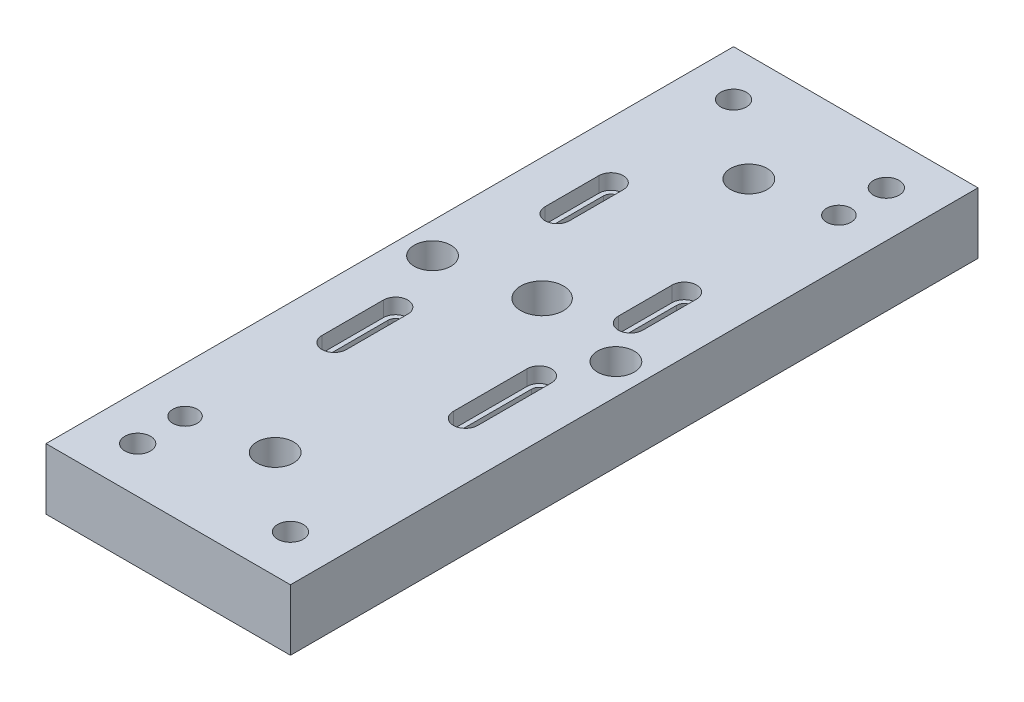
SolidWorks part; units mm, degrees
material "Plain Carbon Steel"
ref_plane "Front Plane" through (0, 0, 0) normal (0, 0, 1) x (1, 0, 0)
ref_plane "Top Plane" through (0, 0, 0) normal (0, 1, 0) x (1, 0, 0)
ref_plane "Right Plane" through (0, 0, 0) normal (1, 0, 0) x (0, 0, -1)
sketch "Sketch1" plane through (0, 0, 0) normal (0, 1, 0) x (1, 0, 0)
  line L1 (-40, -112.5) -> (40, -112.5)
  line L2 (-40, -112.5) -> (-40, 112.5)
  line L3 (-40, 112.5) -> (40, 112.5)
  line L4 (40, -112.5) -> (40, 112.5)
  line L5 (-40, -112.5) -> (40, 112.5) construction
  line L6 (-40, 112.5) -> (40, -112.5) construction
  point P0 (0, 0)
  dimension "D1" = 225
  dimension "D2" = 80
extrude "Boss-Extrude1" add sketch "Sketch1" against normal blind 20
sketch "Sketch2" plane through (0, 0, 0) normal (0, 1, 0) x (1, 0, 0)
  line L4 (24, 17.31) -> (24, 34.91)
  line L5 (19, 34.91) -> (19, 17.31)
  line L6 (24, 17.31) -> (24, 34.91)
  line L7 (19, 34.91) -> (19, 17.31)
  line L10 (24, -36.69) -> (24, -12.59)
  line L11 (19, -12.59) -> (19, -36.69)
  line L12 (24, -36.69) -> (24, -12.59)
  line L13 (19, -12.59) -> (19, -36.69)
  line L16 (-24, -16.59) -> (-24, -36.69)
  line L17 (-19, -36.69) -> (-19, -16.59)
  line L18 (-24, -16.59) -> (-24, -36.69)
  line L19 (-19, -36.69) -> (-19, -16.59)
  line L22 (-24, 53.91) -> (-24, 36.31)
  line L23 (-19, 36.31) -> (-19, 53.91)
  line L24 (-24, 53.91) -> (-24, 36.31)
  line L25 (-19, 36.31) -> (-19, 53.91)
  arc A4 (24, 34.91) -> (19, 34.91) centre (21.5, 34.91) ccw
  arc A5 (19, 17.31) -> (24, 17.31) centre (21.5, 17.31) ccw
  arc A6 (24, 34.91) -> (19, 34.91) centre (21.5, 34.91) ccw
  arc A7 (19, 17.31) -> (24, 17.31) centre (21.5, 17.31) ccw
  arc A10 (24, -12.59) -> (19, -12.59) centre (21.5, -12.59) ccw
  arc A11 (19, -36.69) -> (24, -36.69) centre (21.5, -36.69) ccw
  arc A12 (24, -12.59) -> (19, -12.59) centre (21.5, -12.59) ccw
  arc A13 (19, -36.69) -> (24, -36.69) centre (21.5, -36.69) ccw
  arc A16 (-24, -36.69) -> (-19, -36.69) centre (-21.5, -36.69) ccw
  arc A17 (-19, -16.59) -> (-24, -16.59) centre (-21.5, -16.59) ccw
  arc A18 (-24, -36.69) -> (-19, -36.69) centre (-21.5, -36.69) ccw
  arc A19 (-19, -16.59) -> (-24, -16.59) centre (-21.5, -16.59) ccw
  arc A22 (-24, 36.31) -> (-19, 36.31) centre (-21.5, 36.31) ccw
  arc A23 (-19, 53.91) -> (-24, 53.91) centre (-21.5, 53.91) ccw
  arc A24 (-24, 36.31) -> (-19, 36.31) centre (-21.5, 36.31) ccw
  arc A25 (-19, 53.91) -> (-24, 53.91) centre (-21.5, 53.91) ccw
  dimension "D2" = 0.05
  dimension "D1" = 0.05
  dimension "D3" = 0.05
  dimension "D4" = 0.05
extrude "Cut-Extrude1" cut sketch "Sketch2" against normal up to next
sketch "Sketch3" plane through (0, 0, 0) normal (0, 1, 0) x (1, 0, 0)
  line L4 (-17.5, 36.31) -> (-17.5, 53.91)
  line L5 (-25.5, 53.91) -> (-25.5, 36.31)
  line L6 (-17.5, 36.31) -> (-17.5, 53.91)
  line L7 (-25.5, 53.91) -> (-25.5, 36.31)
  line L10 (25.5, 17.31) -> (25.5, 34.91)
  line L11 (17.5, 34.91) -> (17.5, 17.31)
  line L12 (25.5, 17.31) -> (25.5, 34.91)
  line L13 (17.5, 34.91) -> (17.5, 17.31)
  line L16 (25.5, -36.69) -> (25.5, -12.59)
  line L17 (17.5, -12.59) -> (17.5, -36.69)
  line L18 (25.5, -36.69) -> (25.5, -12.59)
  line L19 (17.5, -12.59) -> (17.5, -36.69)
  line L22 (-25.5, -16.59) -> (-25.5, -36.69)
  line L23 (-17.5, -36.69) -> (-17.5, -16.59)
  line L24 (-25.5, -16.59) -> (-25.5, -36.69)
  line L25 (-17.5, -36.69) -> (-17.5, -16.59)
  arc A4 (-17.5, 53.91) -> (-25.5, 53.91) centre (-21.5, 53.91) ccw
  arc A5 (-25.5, 36.31) -> (-17.5, 36.31) centre (-21.5, 36.31) ccw
  arc A6 (-17.5, 53.91) -> (-25.5, 53.91) centre (-21.5, 53.91) ccw
  arc A7 (-25.5, 36.31) -> (-17.5, 36.31) centre (-21.5, 36.31) ccw
  arc A10 (25.5, 34.91) -> (17.5, 34.91) centre (21.5, 34.91) ccw
  arc A11 (17.5, 17.31) -> (25.5, 17.31) centre (21.5, 17.31) ccw
  arc A12 (25.5, 34.91) -> (17.5, 34.91) centre (21.5, 34.91) ccw
  arc A13 (17.5, 17.31) -> (25.5, 17.31) centre (21.5, 17.31) ccw
  arc A16 (25.5, -12.59) -> (17.5, -12.59) centre (21.5, -12.59) ccw
  arc A17 (17.5, -36.69) -> (25.5, -36.69) centre (21.5, -36.69) ccw
  arc A18 (25.5, -12.59) -> (17.5, -12.59) centre (21.5, -12.59) ccw
  arc A19 (17.5, -36.69) -> (25.5, -36.69) centre (21.5, -36.69) ccw
  arc A22 (-25.5, -36.69) -> (-17.5, -36.69) centre (-21.5, -36.69) ccw
  arc A23 (-17.5, -16.59) -> (-25.5, -16.59) centre (-21.5, -16.59) ccw
  arc A24 (-25.5, -36.69) -> (-17.5, -36.69) centre (-21.5, -36.69) ccw
  arc A25 (-17.5, -16.59) -> (-25.5, -16.59) centre (-21.5, -16.59) ccw
  dimension "D1" = 1.5
  dimension "D2" = 1.5
  dimension "D3" = 1.5
  dimension "D4" = 1.5
extrude "Cut-Extrude2" cut sketch "Sketch3" against normal blind 5
hole_wizard "CBORE for M8 Hex Socket Head Cap Screw1" positions "Sketch7" profile "Sketch6" counterbore size "M8" standard "ISO" end condition through all
sketch "Sketch7" plane through (0, -20, 0) normal (0, -1, 0) x (-1, 0, 0)
  line L0 (-40, -112.5) -> (-40, 112.5) construction
  line L1 (-40, 112.5) -> (40, 112.5) construction
  line L2 (40, 112.5) -> (40, -112.5) construction
  line L3 (40, -112.5) -> (-40, -112.5) construction
  point P0 (-25, 97.5)
  point P2 (25, 97.5)
  point P4 (25, -97.5)
  point P6 (-25, -97.5)
  dimension "D1" = 15
  dimension "D2" = 15
  dimension "D3" = 15
  dimension "D4" = 15
sketch "Sketch6" plane through (25, -20, -97.5) normal (1, 0, 0) x (0, 0, -1)
  line L0 (0, 0) -> (0, 20)
  line L1 (0, 20) -> (4.2, 20)
  line L3 (4.2, 20) -> (4.2, 8.6)
  line L4 (7.5, 8.6) -> (4.2, 8.6)
  line L5 (7.5, 8.6) -> (7.5, 0.025)
  line L6 (7.5, 0.025) -> (7.525, 0)
  line L7 (7.525, 0) -> (0, 0)
  line L8 (-7.5, 0.025) -> (-7.525, 0) construction
  line L11 (0, -6.35) -> (0, 107.95) construction
  dimension "Thru Hole Dia." = 8.4
  dimension "Thru Hole Depth" = 20
  dimension "C'Bore Dia." = 15
  dimension "C'Bore Depth" = 8.6
  dimension "Near C'Sink Dia." = 15.05
  dimension "Near C'Sink Angle" = 90
hole_wizard "Ø8.0mm Dowel Hole1" positions "Sketch12" profile "Sketch9" hole size "Ø8.0" standard "ISO" end condition through all
sketch "Sketch12" plane through (0, -20, 0) normal (0, -1, 0) x (-1, 0, 0)
  line L4 (25, -97.5) -> (25, -82) construction
  line L6 (-25, 97.5) -> (-25, 81.975) construction
  circle A1 centre (25, -97.5) radius 7.5 construction
  circle A3 centre (-25, 97.5) radius 7.525 construction
  point P0 (-25, 81.975)
  point P2 (25, -82)
  dimension "D1" = 8
  dimension "D2" = 8
sketch "Sketch9" plane through (25, -20, -81.975) normal (1, 0, 0) x (0, 0, -1)
  line L0 (0, 0) -> (0, 20)
  line L1 (0, 20) -> (4, 20)
  line L2 (4, 20) -> (4, 0)
  line L5 (4, 0) -> (0, 0)
  line L11 (0, -6.35) -> (0, 107.95) construction
  dimension "Thru Hole Dia." = 8
  dimension "Thru Hole Depth" = 20
sketch "Sketch11" plane through (0, -20, 0) normal (0, -1, 0) x (1, 0, 0)
  circle A0 centre (-22, 55) radius 10.5
  circle A1 centre (22, 55) radius 10.5
  circle A2 centre (-22, -72) radius 10.5
  circle A3 centre (22, -60) radius 10.5
  circle A4 centre (0, -35) radius 10.5
  circle A5 centre (0, 25) radius 10.5
  dimension "D1" = 21
  dimension "D2" = 35
  dimension "D3" = 25
  dimension "D4" = 72
  dimension "D5" = 22
  dimension "D6" = 22
  dimension "D7" = 55
  dimension "D8" = 60
extrude "Cut-Extrude3" cut sketch "Sketch11" against normal blind 14.2
sketch "Sketch13" plane through (0, 0, 0) normal (0, 1, 0) x (1, 0, 0)
  circle A0 centre (0, 77.5) radius 6
  circle A1 centre (0, -77.5) radius 6
  circle A2 centre (-30, 4) radius 6
  circle A3 centre (30, 4) radius 6
  dimension "D1" = 12
extrude "Cut-Extrude4" cut sketch "Sketch13" against normal up to next
sketch "Sketch14" plane through (0, 0, 0) normal (0, 1, 0) x (1, 0, 0)
  circle A0 centre (0, 9.86) radius 5 construction
  circle A1 centre (0, 9.86) radius 5 construction
  circle A2 centre (0, 9.86) radius 7
  dimension "D1" = 14
extrude "Cut-Extrude5" cut sketch "Sketch14" against normal up to next
